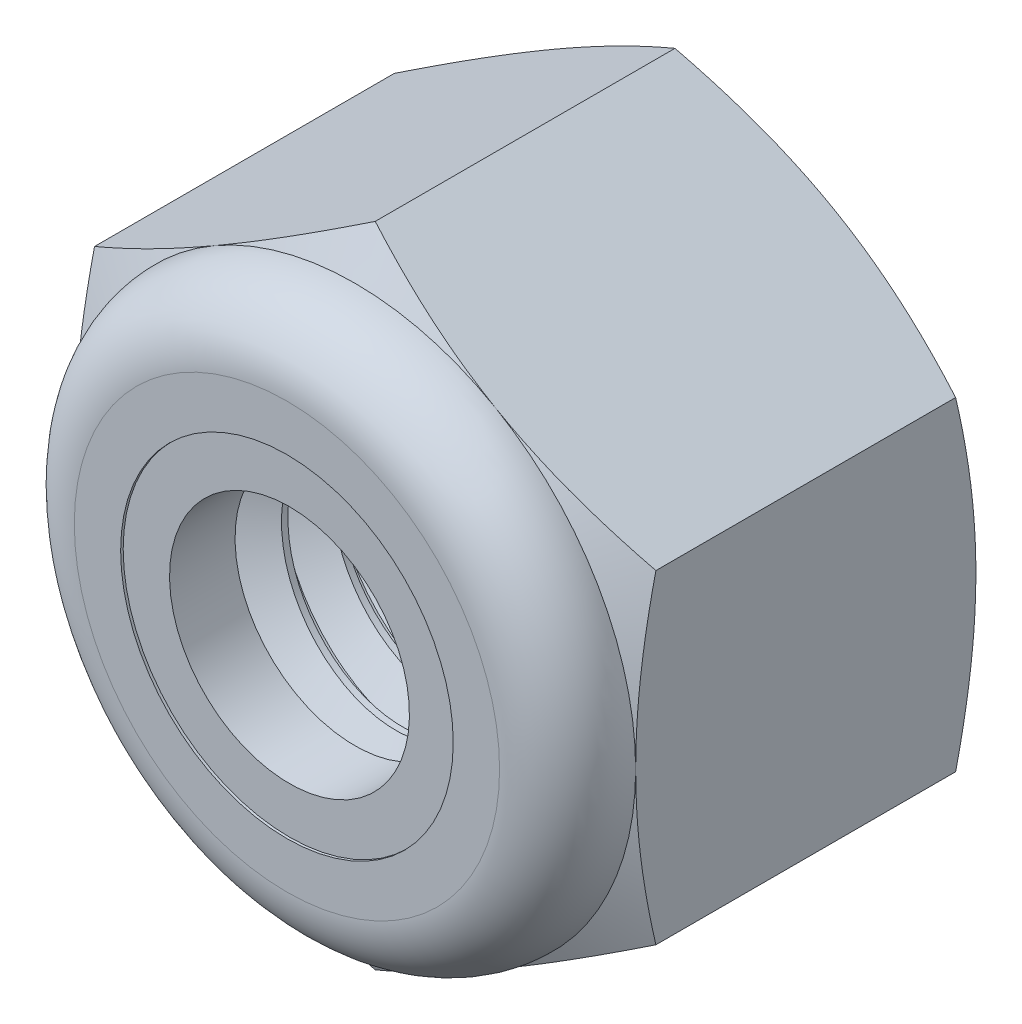
SolidWorks part; units mm, degrees
ref_plane "Front Plane" through (0, 0, 0) normal (0, 0, 1) x (1, 0, 0)
ref_plane "Top Plane" through (0, 0, 0) normal (0, 1, 0) x (1, 0, 0)
ref_plane "Right Plane" through (0, 0, 0) normal (1, 0, 0) x (0, 0, -1)
sketch "Sketch1" plane through (0, 0, 0) normal (0, 0, 1) x (1, 0, 0)
  line L1 (0, 3.1754) -> (-2.75, 1.5877)
  line L2 (-2.75, 1.5877) -> (-2.75, -1.5877)
  line L3 (-2.75, -1.5877) -> (0, -3.1754)
  line L4 (0, -3.1754) -> (2.75, -1.5877)
  line L5 (2.75, -1.5877) -> (2.75, 1.5877)
  line L6 (2.75, 1.5877) -> (0, 3.1754)
  circle A0 centre (0, 0) radius 2.75 construction
  circle A1 centre (0, 0) radius 1.5
  point P10 (0, -1.5)
  point P11 (0, 1.5)
  point P12 (0, 2.75)
  dimension "Thread Size" = 3
  dimension "Width" = 5.5
sketch "Sketch2" plane through (0, 0, 0) normal (1, 0, 0) x (0, 0, -1)
  line L0 (2, 0) -> (-2, 0) construction
  line L1 (-2, 1.5) -> (2, 1.5) construction
  line L2 (-1.975, -1.6293) -> (-3.27, -1.6293) construction
  line L3 (-2.4688, 1.5541) -> (-1.9688, 1.5541) construction
  line L4 (-1.9688, 1.5541) -> (-2.2188, 1.1211) construction
  line L5 (-2.2188, 1.1211) -> (-2.4688, 1.5541) construction
  line L6 (-2.4375, 1.5) -> (-2, 1.5) construction
  line L7 (-2.25, 1.1752) -> (-2.1875, 1.1752) construction
  line L8 (-2.2188, 1.1752) -> (-2.2188, 1.1211) construction
  line L9 (-2.2188, 1.5) -> (-2.2188, 1.5541) construction
  line L10 (-1.9844, 1.5271) -> (-2.4531, 1.5271)
  line L11 (-2.4531, 1.5271) -> (-2.25, 1.1752)
  line L12 (-2.25, 1.1752) -> (-2.1875, 1.1752)
  line L13 (-2.1875, 1.1752) -> (-1.9844, 1.5271)
  line L14 (2, 0) -> (3.27, 0)
  line L15 (3.27, 0) -> (3.27, 4.4454)
  line L16 (0, 4.4454) -> (0, 3.1754) construction
  line L17 (0, 3.1754) -> (0, 1.5877) construction
  line L18 (2, 2.75) -> (-1.3333, 2.75) construction
  line L19 (-2.25, -1.1752) -> (-2.1875, -1.1752) construction
  line L20 (2, 2.75) -> (2, 0)
  line L21 (1.8016, 3.1754) -> (-1.135, 3.1754)
  line L22 (2, 2.75) -> (1.8016, 3.1754)
  line L23 (-2, 0) -> (-2, 2.0833) construction
  line L24 (-1.3333, 2.75) -> (-1.135, 3.1754)
  line L25 (3.27, 4.4454) -> (-3.27, 4.4454)
  line L26 (-2, 2.0833) -> (-3.27, 2.0833)
  line L27 (-3.27, 2.0833) -> (-3.27, 4.4454)
  line L28 (-1.975, 2.0833) -> (-1.975, 1.1752) construction
  line L29 (-1.975, 1.6293) -> (-3.27, 1.6293)
  line L30 (-3.27, 1.6293) -> (-3.27, 0)
  line L31 (-3.27, 0) -> (-1.3333, 0)
  line L32 (-1.3333, 0) -> (-1.3333, 2.725)
  line L33 (-1.975, 1.6293) -> (-1.975, 2.0833)
  arc A0 (-1.3333, 2.75) -> (-2, 2.0833) centre (-1.3333, 2.0833) ccw
  arc A1 (-1.3333, 2.725) -> (-1.975, 2.0833) centre (-1.3333, 2.0833) ccw
  point P4 (0, 0)
  point P18 (-2.2188, 1.5271)
  point P22 (-2.2188, 1.5271)
  point P33 (0, 3.1754)
  point P48 (-3.27, -1.6293)
  point P51 (-2.25, -1.1752)
  dimension "Height" = 4
  dimension "Pitch" = 0.5
  dimension "D1" = 0.0625
  dimension "D2" = 1.27
  dimension "D3" = 25
  dimension "D4" = 0.6667
  dimension "D5" = 25
  dimension "D6" = 0.025
sketch "Sketch3" plane through (0, 0, 0) normal (0, 0, 1) x (1, 0, 0)
  line L0 (0, -3.1754) -> (2.75, -1.5877) construction
  line L1 (2.75, -1.5877) -> (2.75, 1.5877) construction
  line L2 (2.75, 1.5877) -> (0, 3.1754) construction
  line L3 (0, 3.1754) -> (-2.75, 1.5877) construction
  line L4 (-2.75, 1.5877) -> (-2.75, -1.5877) construction
  line L5 (-2.75, -1.5877) -> (0, -3.1754) construction
  line L6 (0, -3.1754) -> (2.75, -1.5877)
  line L7 (2.75, -1.5877) -> (2.75, 1.5877)
  line L8 (2.75, 1.5877) -> (0, 3.1754)
  line L9 (0, 3.1754) -> (-2.75, 1.5877)
  line L10 (-2.75, 1.5877) -> (-2.75, -1.5877)
  line L11 (-2.75, -1.5877) -> (0, -3.1754)
  circle A0 centre (0, 0) radius 1.5 construction
  circle A1 centre (0, 0) radius 1.5
extrude "Boss-Extrude1" add sketch "Sketch3" along normal mid plane 4
sketch "Sketch4" plane through (0, 0, 0) normal (1, 0, 0) x (0, 0, -1)
  line L0 (3.27, 4.4454) -> (-3.27, 4.4454) construction
  line L1 (-3.27, 2.0833) -> (-3.27, 4.4454) construction
  line L2 (-2, 2.0833) -> (-3.27, 2.0833) construction
  line L3 (-1.3333, 2.75) -> (-1.135, 3.1754) construction
  line L4 (1.8016, 3.1754) -> (-1.135, 3.1754) construction
  line L5 (2, 2.75) -> (1.8016, 3.1754) construction
  line L6 (2, 2.75) -> (2, 0) construction
  line L7 (2, 0) -> (3.27, 0) construction
  line L8 (3.27, 0) -> (3.27, 4.4454) construction
  line L9 (-3.27, 1.6293) -> (-3.27, 0) construction
  line L10 (-3.27, 0) -> (-1.3333, 0) construction
  line L11 (-1.3333, 0) -> (-1.3333, 2.725) construction
  line L12 (-1.975, 1.6293) -> (-1.975, 2.0833) construction
  line L13 (-1.975, 1.6293) -> (-3.27, 1.6293) construction
  line L14 (3.27, 4.4454) -> (-3.27, 4.4454)
  line L15 (-3.27, 2.0833) -> (-3.27, 4.4454)
  line L16 (-2, 2.0833) -> (-3.27, 2.0833)
  line L17 (-1.3333, 2.75) -> (-1.135, 3.1754)
  line L18 (1.8016, 3.1754) -> (-1.135, 3.1754)
  line L19 (2, 2.75) -> (1.8016, 3.1754)
  line L20 (2, 2.75) -> (2, 0)
  line L21 (2, 0) -> (3.27, 0)
  line L22 (3.27, 0) -> (3.27, 4.4454)
  line L23 (-3.27, 1.6293) -> (-3.27, 0)
  line L24 (-3.27, 0) -> (-1.3333, 0)
  line L25 (-1.3333, 0) -> (-1.3333, 2.725)
  line L26 (-1.975, 1.6293) -> (-1.975, 2.0833)
  line L27 (-1.975, 1.6293) -> (-3.27, 1.6293)
  arc A0 (-1.3333, 2.75) -> (-2, 2.0833) centre (-1.3333, 2.0833) ccw construction
  arc A1 (-1.3333, 2.725) -> (-1.975, 2.0833) centre (-1.3333, 2.0833) ccw construction
  arc A2 (-1.3333, 2.75) -> (-2, 2.0833) centre (-1.3333, 2.0833) ccw
  arc A3 (-1.3333, 2.725) -> (-1.975, 2.0833) centre (-1.3333, 2.0833) ccw
revolve "Cut-Revolve1" cut sketch "Sketch4" angle 360 about L0
sketch "Sketch5" plane through (0, 0, 0) normal (1, 0, 0) x (0, 0, -1)
  line L0 (-1.975, 2.0833) -> (-1.975, 1.1752) construction
  line L1 (-1.3333, 0) -> (-1.3333, 2.725) construction
  line L2 (-1.975, 2.0833) -> (-1.975, 1.1752)
  line L3 (-1.3333, 1.1752) -> (-1.3333, 2.725)
  line L4 (-1.975, 1.1752) -> (-1.3333, 1.1752)
  arc A0 (-1.3333, 2.725) -> (-1.975, 2.0833) centre (-1.3333, 2.0833) ccw construction
  arc A1 (-1.3333, 2.725) -> (-1.975, 2.0833) centre (-1.3333, 2.0833) ccw
revolve "Revolve1" add sketch "Sketch5" angle 360 about L0
sketch "Sketch6" plane through (0, 0, 2) normal (0, 0, 1) x (1, 0, 0)
  circle A0 centre (0, 0) radius 1.5 construction
  circle A1 centre (0, 0) radius 1.5
curve "Helix/Spiral1" pitch 0.5 height 4.5 radius 1.5 centre (0, 0, 2) axis (0, 0, -1) start towards (0, 1, 0)
sketch "Sketch7" plane through (0, 0, 0) normal (1, 0, 0) x (0, 0, -1)
  line L0 (-2.4531, 1.5271) -> (-2.25, 1.1752) construction
  line L1 (-2.25, 1.1752) -> (-2.1875, 1.1752) construction
  line L2 (-2.1875, 1.1752) -> (-1.9844, 1.5271) construction
  line L3 (-1.9844, 1.5271) -> (-2.4531, 1.5271) construction
  line L4 (-2.4531, 1.5271) -> (-2.25, 1.1752)
  line L5 (-2.25, 1.1752) -> (-2.1875, 1.1752)
  line L6 (-2.1875, 1.1752) -> (-1.9844, 1.5271)
  line L7 (-1.9844, 1.5271) -> (-2.4531, 1.5271)
sweep "Sweep1" add profiles "Sketch7" path "Helix/Spiral1"
sketch "Sketch8" plane through (0, 0, -2) normal (0, 0, -1) x (-1, 0, 0)
  circle A2 centre (0, 0) radius 1.5271
  point P2 (0, 1.5271)
extrude "Cut-Extrude1" cut sketch "Sketch8" along normal through all and the other way through all draft 60
sketch "Sketch9" plane through (0, 0, 1.3333) normal (0, 0, 1) x (1, 0, 0)
  circle A2 centre (0, 0) radius 1.5271
  circle A3 centre (0, 0) radius 1.1752 construction
  point P2 (0, 1.5271)
  point P4 (0, 1.1752)
extrude "Cut-Extrude2" cut sketch "Sketch9" along normal through all and the other way through all draft 60
equation "\"D1@Sketch2\" = \"Pitch@Sketch2\" / 8"
equation "\"D4@Sketch2\"=\"Height@Sketch2\"/6"
equation "\"D1@Boss-Extrude1\"=\"Height@Sketch2\""
equation "\"D3@Helix/Spiral1\"=\"Height@Sketch2\"+\"Pitch@Sketch2\""
equation "\"D4@Helix/Spiral1\"=\"Pitch@Sketch2\""
equation "\"D6@Sketch2\"=\"Pitch@Sketch2\"*0.05"
